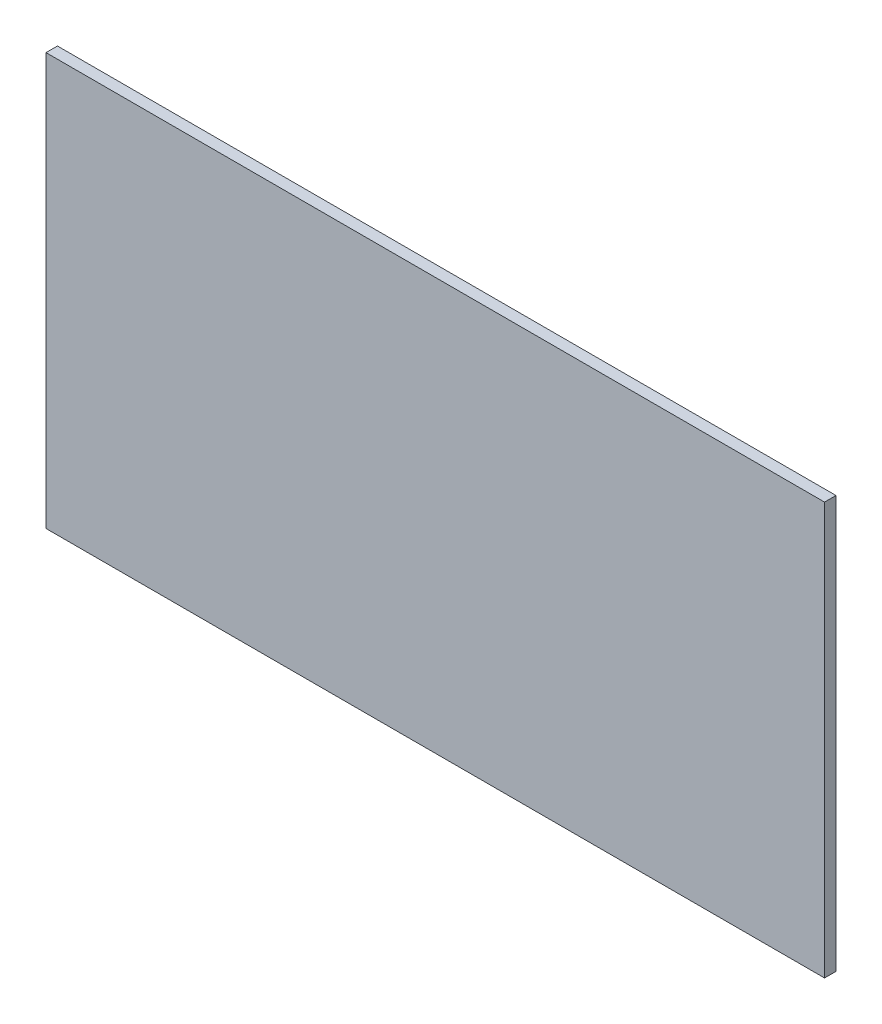
SolidWorks part; units mm, degrees
material "Custom Plastic"
ref_plane "X-Y Datum" through (0, 0, 0) normal (0, 0, 1) x (1, 0, 0)
ref_plane "X-Z Datum" through (0, 0, 0) normal (0, 1, 0) x (1, 0, 0)
ref_plane "Y-Z Datum" through (0, 0, 0) normal (1, 0, 0) x (0, 0, -1)
sketch "Sketch1" plane through (0, 0, 0) normal (0, 0, 1) x (1, 0, 0)
  line L1 (-53.975, 28.575) -> (53.975, 28.575)
  line L2 (-53.975, 28.575) -> (-53.975, -28.575)
  line L3 (-53.975, -28.575) -> (53.975, -28.575)
  line L4 (53.975, 28.575) -> (53.975, -28.575)
  line L5 (-53.975, 28.575) -> (53.975, -28.575) construction
  line L6 (-53.975, -28.575) -> (53.975, 28.575) construction
  point P0 (0, 0)
  dimension "D1" = 107.95
  dimension "D2" = 57.15
extrude "Boss-Extrude1" add sketch "Sketch1" along normal blind 1.5875
